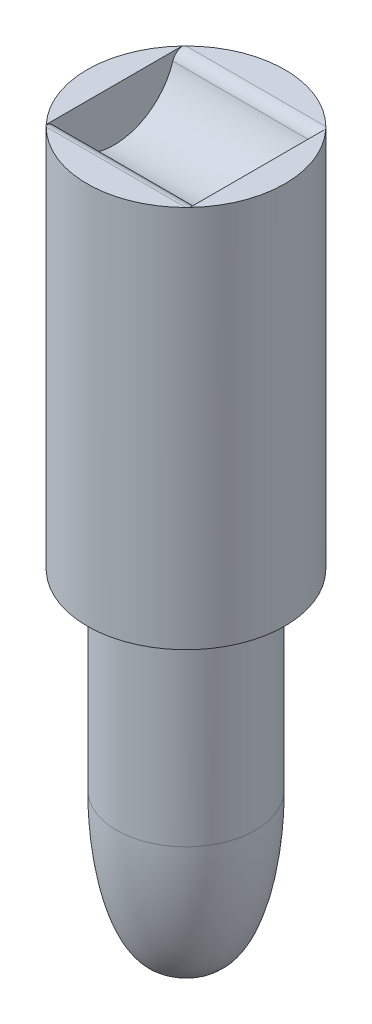
SolidWorks part; units mm, degrees
ref_plane "Front Plane" through (0, 0, 0) normal (0, 0, 1) x (1, 0, 0)
ref_plane "Top Plane" through (0, 0, 0) normal (0, 1, 0) x (1, 0, 0)
ref_plane "Right Plane" through (0, 0, 0) normal (1, 0, 0) x (0, 0, -1)
sketch "Sketch1" plane through (0, 0, 0) normal (0, 1, 0) x (1, 0, 0)
  circle A0 centre (0, 0) radius 1.65 construction
  circle A1 centre (0, 0) radius 1.45
  dimension "D1" = 3.3
  dimension "D2" = 0.2
extrude "Boss-Extrude1" add sketch "Sketch1" along normal blind 7
sketch "Sketch3" plane through (0, 7, 0) normal (0, 1, 0) x (1, 0, 0)
  circle A0 centre (0, 0) radius 2.265 construction
  circle A1 centre (0, 0) radius 2.065
  circle A2 centre (0, 0) radius 2.265 construction
  dimension "D2" = 0.2
extrude "Boss-Extrude3" add sketch "Sketch3" along normal blind 8
fillet "Fillet1" radius 1 1 edges at (0, 0, 1.45) second distance 3 first distance on face at (0, 0, 1.45)
sketch "master dent sketch" plane through (0, 0, 0) normal (1, 0, 0) x (0, 0, -1)
  line L0 (2.065, 15) -> (-2.065, 15) construction
  line L1 (2.065, 15) -> (-2.065, 15)
  line L2 (1.265, 15) -> (1.4176, 15.9655)
  line L3 (-1.265, 15) -> (-1.4176, 15.9655)
  line L4 (-1.265, 15) -> (-1.265, 15.7542)
  circle A0 centre (0, 15.2) radius 1.2807
  point P8 (0, 0)
  point P9 (0, 15)
  point P11 (-1.4609, 15.4148)
  point P12 (-2.2178, 16.2277)
  dimension "D1" = 0.8
  dimension "D2" = 0.2
  dimension "D3" = 81.016
  dimension "D4" = 8.984
sketch "Sketch5" plane through (0, 0, 0) normal (1, 0, 0) x (0, 0, -1)
  circle A0 centre (0, 15.2) radius 1.2807 construction
  circle A1 centre (0, 15.2) radius 1.2807
extrude "Cut-Extrude1" cut sketch "Sketch5" against normal blind 1.5 and the other way blind 1.5
ref_axis "Axis1" through (1.5, 15.2, 0) along (-1, 0, 0)
fillet "Fillet2" radius 0.25 2 edges at (0, 15, -1.265) (0, 15, 1.265)
